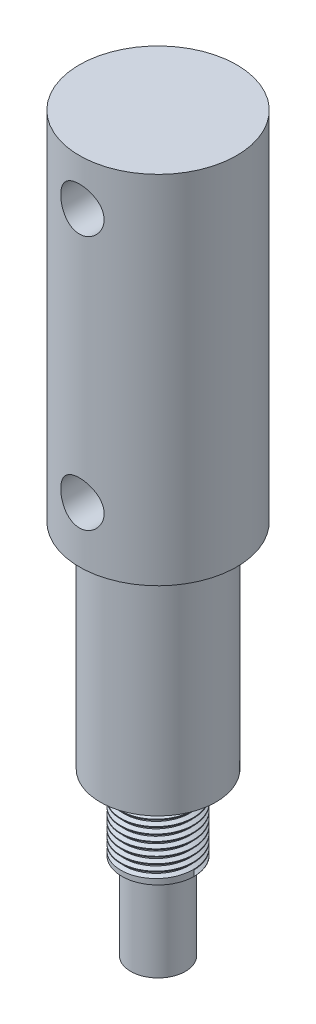
SolidWorks part; units mm, degrees
material "AISI 316 Annealed Stainless Steel Bar (SS)"
ref_plane "Front Plane" through (0, 0, 0) normal (0, 0, 1) x (1, 0, 0)
ref_plane "Top Plane" through (0, 0, 0) normal (0, 1, 0) x (1, 0, 0)
ref_plane "Right Plane" through (0, 0, 0) normal (1, 0, 0) x (0, 0, -1)
sketch "Sketch2" plane through (0, 0, 0) normal (0, 0, 1) x (1, 0, 0)
  line L0 (0, 0) -> (0, 508.8276) construction
  line L1 (0, 0) -> (6, 0)
  line L2 (0, 0) -> (0, 19.05)
  line L3 (0, 19.05) -> (6, 19.05)
  line L4 (6, 0) -> (6, 19.05)
  line L5 (0, 19.05) -> (7.9375, 19.05)
  line L6 (0, 19.05) -> (0, 35.56)
  line L7 (0, 35.56) -> (7.9375, 35.56)
  line L8 (7.9375, 19.05) -> (7.9375, 35.56)
  line L9 (0, 35.56) -> (12.721, 35.56)
  line L10 (0, 35.56) -> (0, 82.55)
  line L11 (0, 82.55) -> (12.721, 82.55)
  line L12 (12.721, 35.56) -> (12.721, 82.55)
  line L13 (0, 82.55) -> (17.272, 82.55)
  line L14 (0, 82.55) -> (0, 160.782)
  line L15 (0, 160.782) -> (17.272, 160.782)
  line L16 (17.272, 82.55) -> (17.272, 160.782)
  dimension "D1" = 78.232
  dimension "D2" = 17.272
  dimension "D4" = 46.99
  dimension "D3" = 12.721
  dimension "D5" = 16.51
  dimension "D6" = 7.9375
  dimension "D7" = 19.05
  dimension "D8" = 6
revolve "Revolve1" add sketch "Sketch2" angle 360 about L0 region at (3, 9.525, 0) region at (3.9687, 27.305, 0) region at (6.3605, 59.055, 0) region at (8.636, 121.666, 0)
thread "Thread2" pitch 1.4111 method cut profile "Thread Profile3" start angle 0, offset 0, length 0, pitch 1.4111, diameter 15.875
ref_plane "Plane3" through (7.9375, 19.05, 0) normal (0, 0, 1) x (1, 0, 0)
sketch "Thread Profile3" plane through (7.9375, 19.05, 0) normal (0, 0, 1) x (1, 0, 0)
  line L0 (0, 0) -> (0, 1.4111) construction
  line L11 (0, 0) -> (0, 1.2347)
  line L12 (0, 1.2347) -> (-0.7638, 0.7937)
  line L13 (-0.7638, 0.7937) -> (-0.7638, 0.441)
  line L15 (-0.7638, 0.441) -> (0, 0)
  line L17 (-0.7638, 0.6174) -> (0, 0.6174) construction
  point P2 (0, 0)
  dimension "Pitch" = 1.4111
  dimension "Profile_Angle" = 60
  dimension "Profile_Land" = 0.3528
  dimension "Profile_Height" = 0.7638
sketch "Sketch3" plane through (0, 0, 0) normal (0, 0, 1) x (1, 0, 0)
  line L0 (0, 0) -> (0, 197.3408) construction
  line L1 (17.272, 160.782) -> (-17.272, 160.782) construction
  circle A0 centre (0, 150.622) radius 4.7625
  circle A1 centre (0, 94.742) radius 4.7625
  dimension "D1" = 9.525
  dimension "D2" = 10.16
  dimension "D3" = 66.04
extrude "Cut-Extrude1" cut sketch "Sketch3" against normal through all both and the other way through all
equation "\"hole diamiter\"= 1.36in"
equation "\"wheel depth\"= 2.88"
equation "\"press_tolerance\"= 0.00165"
equation "\"wheel_connection\"= \"hole diamiter\"'https://at-machining.com/tolerance-press-fit/"
equation "\"D1@Sketch2\"=\"wheel depth\"+0.2"
equation "\"D2@Sketch2\"=\"wheel_connection\"/2"
equation "\"fitting depth\"= 1.85"
equation "\"D4@Sketch2\"=\"fitting depth\""
equation "\"bearing_id\"= 1"
equation "\"bearing_connection\"= \"bearing_id\" + \"press_tolerance\"'https://at-machining.com/tolerance-press-fit/"
equation "\"D3@Sketch2\"=\"bearing_connection\"/2"
equation "\"thread length\"= 0.65"
equation "\"major_diamiter\"= 5 / 8'https://www.machiningdoctor.com/threadinfo/?tid=81"
equation "\"D5@Sketch2\"=\"thread length\""
equation "\"D6@Sketch2\"=\"major_diamiter\"/2"
equation "\"coupling diamiter\"= 12mm"
equation "\"coupling lenght\"= 1.5 / 2"
equation "\"D7@Sketch2\"=\"coupling lenght\""
equation "\"D8@Sketch2\"=\"coupling diamiter\"/2"
